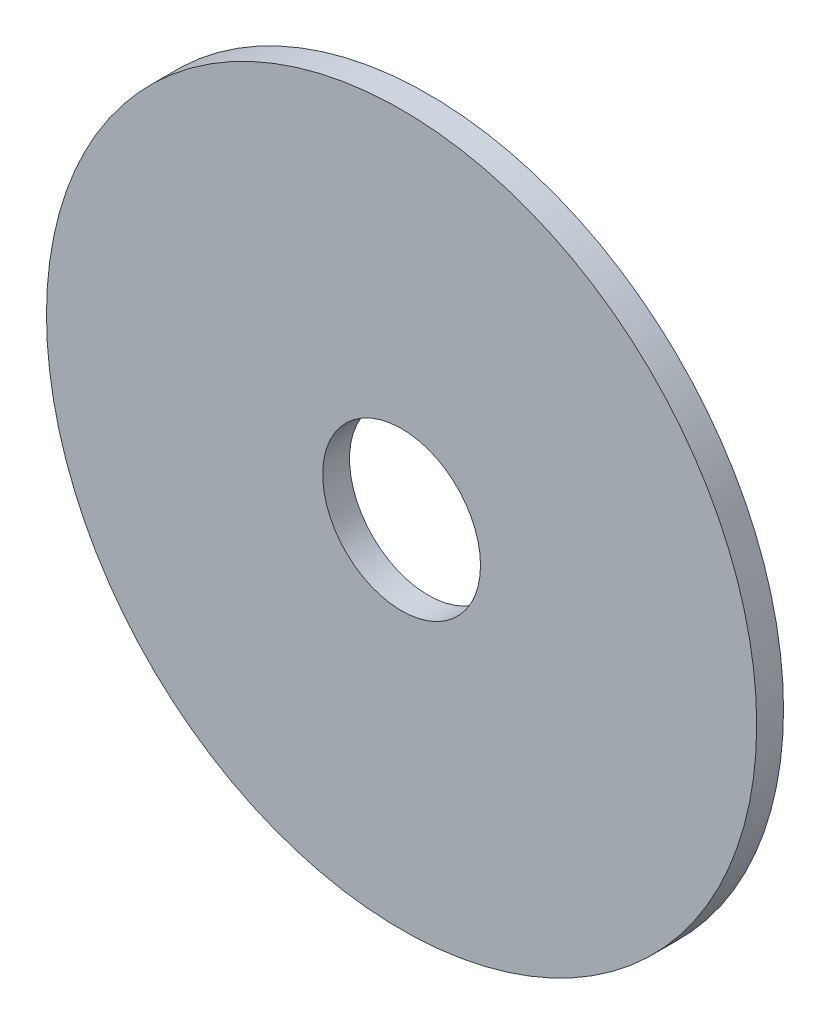
SolidWorks part; units mm, degrees
material "ABS PC"
ref_plane "Front Plane" through (0, 0, 0) normal (0, 0, 1) x (1, 0, 0)
ref_plane "Top Plane" through (0, 0, 0) normal (0, 1, 0) x (1, 0, 0)
ref_plane "Right Plane" through (0, 0, 0) normal (1, 0, 0) x (0, 0, -1)
sketch "Sketch1" plane through (0, 0, 0) normal (0, 0, 1) x (1, 0, 0)
  circle A0 centre (0, 0) radius 22.5
  circle A1 centre (0, 0) radius 5
  dimension "D1" = 45
  dimension "D2" = 10
extrude "Boss-Extrude1" add sketch "Sketch1" along normal blind 1.7
equation "\"smallPulleyTeeth\"= 15"
equation "\"largePulleyTeeth\"= 40"
equation "\"eighthThick\"= 2.9mm"
equation "\"sixteenthThick\"= 1.7mm"
equation "\"wheelEighthThick\"=3.0mm"
equation "\"quarterThick\"=5.9mm"
equation "\"bushingDiam\"= 7.85mm"
equation "\"plateBoltCircle\"= 65mm"
equation "\"plateBoltDiam\"= 5mm"
equation "\"D1@Boss-Extrude1\"=\"sixteenthThick\""
